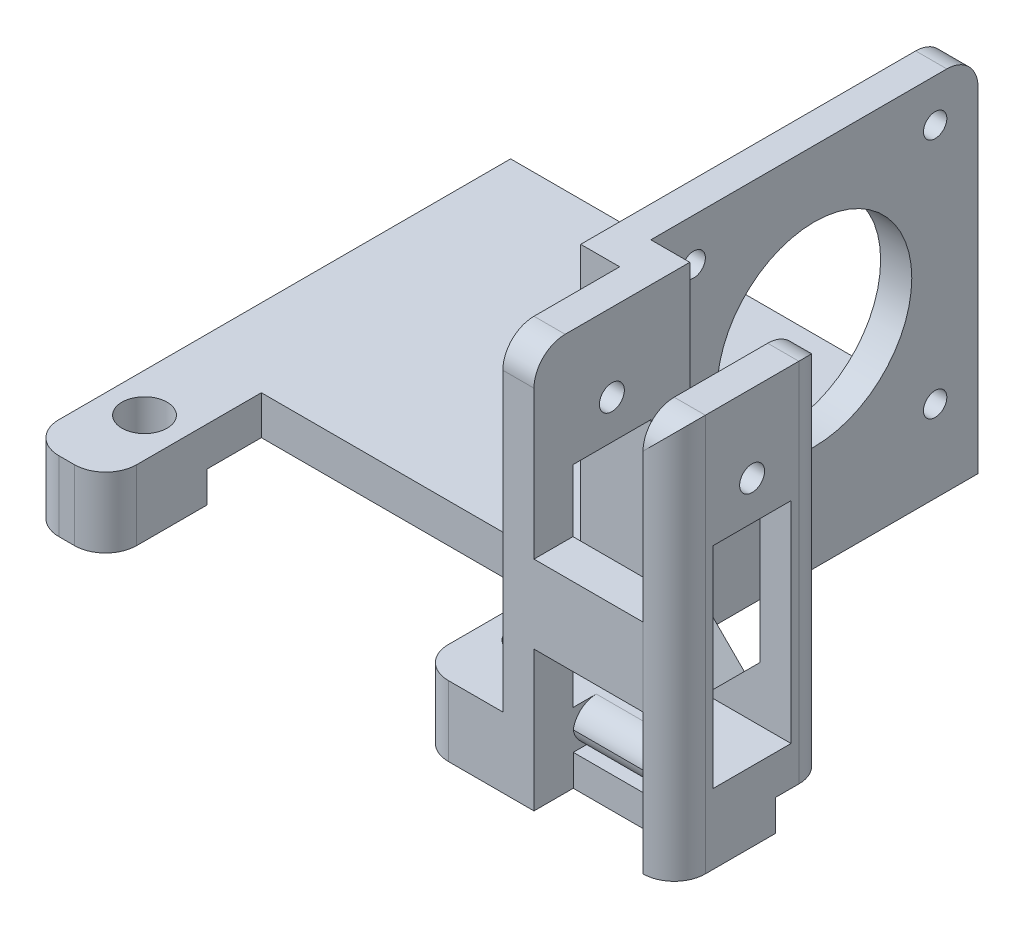
SolidWorks part; units mm, degrees
ref_plane "前视基准面" through (0, 0, 0) normal (0, 0, 1) x (1, 0, 0)
ref_plane "上视基准面" through (0, 0, 0) normal (0, 1, 0) x (1, 0, 0)
ref_plane "右视基准面" through (0, 0, 0) normal (1, 0, 0) x (0, 0, -1)
other "Configuration Table"
sketch "草图1" plane through (0, 0, 0) normal (0, 1, 0) x (1, 0, 0)
  line L1 (10, 0) -> (50, 0)
  line L2 (0, 0) -> (0, 42)
  line L3 (0, 42) -> (60, 42)
  line L4 (60, 0) -> (60, 42)
  line L6 (0, 0) -> (0, -20)
  line L7 (0, -20) -> (10, -20)
  line L8 (10, 0) -> (10, -20)
  line L14 (60, 0) -> (60, -20)
  line L15 (60, -20) -> (50, -20)
  line L16 (50, 0) -> (50, -20)
  point P11 (5, -20)
  dimension "D1" = 10
  dimension "D2" = 60
  dimension "D3" = 42
  dimension "D4" = 20
  dimension "D5" = 20
  dimension "D6" = 10
  dimension "D7" = 20
extrude "凸台-拉伸1" add sketch "草图1" along normal blind 5
sketch "草图3" plane through (0, 5, 0) normal (0, 1, 0) x (1, 0, 0)
  line L1 (56, 0) -> (60, 0)
  line L2 (56, 0) -> (56, 42)
  line L3 (56, 42) -> (60, 42)
  line L4 (60, 0) -> (60, 42)
  dimension "D1" = 4
extrude "凸台-拉伸2" add sketch "草图3" along normal blind 42
sketch "草图4" plane through (56, 0, 0) normal (-1, 0, 0) x (0, 0, 1)
  line L0 (-42, 47) -> (-36.5, 47) construction
  line L1 (-42, 47) -> (0, 47) construction
  line L2 (-36.5, 47) -> (-36.5, 41.5) construction
  line L3 (-36.5, 41.5) -> (-5.5, 41.5) construction
  line L4 (-5.5, 41.5) -> (-5.5, 10.5) construction
  line L5 (-5.5, 10.5) -> (-36.5, 10.5) construction
  circle A0 centre (-36.5, 41.5) radius 1.5
  circle A1 centre (-5.5, 41.5) radius 1.5
  circle A2 centre (-5.5, 10.5) radius 1.5
  circle A3 centre (-36.5, 10.5) radius 1.5
  dimension "D6" = 3
  dimension "D1" = 5.5
  dimension "D2" = 5.5
  dimension "D3" = 31
  dimension "D4" = 31
  dimension "D5" = 31
extrude "切除-拉伸1" cut sketch "草图4" against normal blind 42.5
sketch "草图5" plane through (56, 0, 0) normal (-1, 0, 0) x (0, 0, 1)
  line L0 (-42, 47) -> (0, 5) construction
  circle A0 centre (-21, 26) radius 12.5
  dimension "D1" = 25
extrude "切除-拉伸2" cut sketch "草图5" against normal blind 42.5
sketch "草图6" plane through (0, 5, 0) normal (0, 1, 0) x (1, 0, 0)
  line L0 (5, -20) -> (5, -10) construction
  line L1 (0, -20) -> (10, -20) construction
  line L2 (55, -20) -> (55, -10) construction
  line L3 (50, -20) -> (60, -20) construction
  circle A0 centre (55, -10) radius 1.5
  circle A1 centre (5, -10) radius 1.5
  dimension "D3" = 3
  dimension "D4" = 3
  dimension "D1" = 10
  dimension "D2" = 10
extrude "切除-拉伸3" cut sketch "草图6" against normal blind 42.5
sketch "草图7" plane through (60, 0, 0) normal (1, 0, 0) x (0, 0, -1)
  line L1 (-20, 5) -> (0, 5)
  line L2 (-20, 5) -> (-20, 0)
  line L3 (-20, 0) -> (0, 0)
  line L4 (0, 5) -> (0, 0)
extrude "凸台-拉伸3" add sketch "草图7" along normal blind 5
sketch "草图8" plane through (0, 5, 0) normal (0, 1, 0) x (1, 0, 0)
  line L0 (50, -20) -> (65, -20) construction
  line L1 (65, 0) -> (56, 0)
  line L2 (65, 0) -> (65, -20)
  line L3 (65, -20) -> (56, -20)
  line L4 (56, 0) -> (56, -5)
  line L5 (56, -15) -> (56, -20)
  line L6 (56, -5) -> (61, -5)
  line L8 (56, -15) -> (61, -15)
  line L9 (61, -5) -> (61, -15)
  dimension "D1" = 9
  dimension "D2" = 5
  dimension "D3" = 5
  dimension "D4" = 5
extrude "凸台-拉伸5" add sketch "草图8" along normal up to surface (42 mm away) up to face at (58, 47, -21)
sketch "草图11" plane through (65, 0, 0) normal (1, 0, 0) x (0, 0, -1)
  line L4 (-20, 0) -> (0, 0)
  line L5 (-20, 5) -> (-20, 0)
  line L6 (0, 5) -> (-20, 5)
  line L7 (0, 0) -> (0, 5)
  line L8 (-20, 0) -> (0, 0)
  line L9 (-20, 5) -> (-20, 0)
  line L10 (0, 5) -> (-20, 5)
  line L11 (0, 0) -> (0, 5)
  dimension "D1" = 0
extrude "凸台-拉伸6" add sketch "草图11" along normal blind 18
sketch "草图12" plane through (0, 5, 0) normal (0, 1, 0) x (1, 0, 0)
  line L0 (83, -20) -> (65, -20) construction
  line L1 (83, 0) -> (79, 0)
  line L2 (83, 0) -> (83, -20)
  line L3 (83, -20) -> (79, -20)
  line L4 (79, 0) -> (79, -20)
  dimension "D1" = 4
extrude "凸台-拉伸7" add sketch "草图12" along normal up to surface (42 mm away) up to face at (59.6, 47, -0.4)
sketch "草图13" plane through (83, 0, 0) normal (1, 0, 0) x (0, 0, -1)
  line L0 (0, 47) -> (-20, 47) construction
  circle A0 centre (-10, 37) radius 1.6
  dimension "D1" = 10
  dimension "D2" = 3.2
extrude "切除-拉伸4" cut sketch "草图13" against normal up to surface (22 mm away) up to face at (61, 26, 10)
sketch "草图15" plane through (61, 0, 0) normal (-1, 0, 0) x (0, 0, 1)
  line L0 (15, 47) -> (15, 5) construction
  line L1 (5, 5) -> (15, 5)
  line L2 (5, 5) -> (5, 32)
  line L3 (5, 32) -> (15, 32)
  line L4 (15, 5) -> (15, 32)
  circle A0 centre (10, 37) radius 1.6 construction
  dimension "D1" = 5
extrude "切除-拉伸5" cut sketch "草图15" against normal up to surface (22 mm away) up to face at (83, 37, 8.4)
sketch "草图16" plane through (0, 47, 0) normal (0, 1, 0) x (1, 0, 0)
  line L1 (61, -15) -> (56, -15)
  line L2 (61, -15) -> (61, -20)
  line L3 (61, -20) -> (56, -20)
  line L4 (56, -15) -> (56, -20)
extrude "切除-拉伸6" cut sketch "草图16" against normal up to surface (42 mm away) up to face at (55, 5, 11.5)
sketch "草图17" plane through (61, 0, 0) normal (-1, 0, 0) x (0, 0, 1)
  line L0 (5, 47) -> (5, 5) construction
  line L1 (15, 5) -> (5, 5)
  line L2 (15, 5) -> (15, 10)
  line L3 (15, 10) -> (5, 10)
  line L4 (5, 5) -> (5, 10)
  dimension "D1" = 5
extrude "凸台-拉伸8" add sketch "草图17" against normal up to surface (22 mm away) up to face at (83, 18.5, 10)
sketch "草图19" plane through (0, 10, 0) normal (0, 1, 0) x (1, 0, 0)
  line L8 (79, -15) -> (83, -15)
  line L9 (83, -15) -> (83, -5)
  line L10 (83, -5) -> (79, -5)
  line L11 (79, -5) -> (65, -5)
  line L12 (65, -5) -> (61, -5)
  line L13 (61, -5) -> (61, -15)
  line L14 (61, -15) -> (65, -15)
  line L15 (65, -15) -> (79, -15)
  line L16 (79, -15) -> (83, -15)
  line L17 (83, -15) -> (83, -5)
  line L18 (83, -5) -> (79, -5)
  line L19 (79, -5) -> (65, -5)
  line L20 (65, -5) -> (61, -5)
  line L21 (61, -5) -> (61, -15)
  line L22 (61, -15) -> (65, -15)
  line L23 (65, -15) -> (79, -15)
  dimension "D1" = 0
extrude "切除-拉伸7" cut sketch "草图19" against normal up to surface (5 mm away) up to face at (35.4, 5, 0.6)
fillet "圆角1" radius 4 9 edges at (83, 23.5, 0) (83, 23.5, 20) (0, 2.5, 20) (10, 2.5, 20) (50, 2.5, 20) (81, 47, 20) (63, 47, 20) (81, 47, 0) (58, 47, -42)
sketch "草图20" plane through (0, 0, 20) normal (0, 0, 1) x (1, 0, 0)
  line L1 (65, 5) -> (79, 5)
  line L2 (65, 5) -> (65, 0)
  line L3 (65, 0) -> (79, 0)
  line L4 (79, 5) -> (79, 0)
extrude "切除-拉伸8" cut sketch "草图20" against normal blind 5
fillet "圆角3" radius 3 2 edges at (72, 0, 15) (72, 5, 15)
sketch "草图21" plane through (0, 5, 0) normal (0, 1, 0) x (1, 0, 0)
  circle A0 centre (5, -10) radius 2.9
  circle A1 centre (55, -10) radius 2.9
  dimension "D1" = 5.8
  dimension "D2" = 5.8
extrude "切除-拉伸9" cut sketch "草图21" against normal offset from surface (3 mm away) 2 up to face at (55, 0, 11.5)
sketch "草图23" plane through (0, 0, 0) normal (0, -1, 0) x (1, 0, 0)
  line L0 (54, 20) -> (65, 20) construction
  line L1 (4, 20) -> (6, 20) construction
  line L2 (54, 20) -> (65, 20)
  line L3 (4, 20) -> (6, 20)
  line L4 (0, 16) -> (0, 7)
  line L5 (0, -42) -> (0, 16) construction
  line L6 (0, 7) -> (10, 7)
  line L7 (83, 16) -> (83, 4) construction
  line L8 (83, 7) -> (83, 16)
  line L9 (79, 20) -> (79, 14.958)
  line L10 (79, 14.958) -> (65, 14.958)
  line L11 (65, 12) -> (65, 20) construction
  line L12 (65, 14.958) -> (65, 20)
  line L13 (50, 16) -> (50, 7)
  line L14 (50, 0) -> (50, 16) construction
  line L16 (10, 16) -> (10, 0) construction
  line L17 (10, 7) -> (10, 16)
  line L18 (50, 7) -> (83, 7)
  arc A0 (83, 16) -> (79, 20) centre (79, 16) ccw construction
  arc A1 (54, 20) -> (50, 16) centre (54, 16) ccw construction
  arc A2 (10, 16) -> (6, 20) centre (6, 16) ccw construction
  arc A3 (4, 20) -> (0, 16) centre (4, 16) ccw construction
  arc A4 (83, 16) -> (79, 20) centre (79, 16) ccw
  arc A5 (54, 20) -> (50, 16) centre (54, 16) ccw
  arc A6 (10, 16) -> (6, 20) centre (6, 16) ccw
  arc A7 (4, 20) -> (0, 16) centre (4, 16) ccw
  dimension "D1" = 13
  dimension "D2" = 13
extrude "凸台-拉伸9" add sketch "草图23" along normal blind 4
sketch "草图24" plane through (0, 0, 0) normal (0, 1, 0) x (1, 0, 0)
  circle A0 centre (55, -10) radius 1.5 construction
  circle A1 centre (5, -10) radius 1.5 construction
  circle A2 centre (55, -10) radius 1.5
  circle A3 centre (5, -10) radius 1.5
extrude "切除-拉伸10" cut sketch "草图24" against normal blind 4
sketch "草图26" plane through (0, 2, 0) normal (0, 1, 0) x (1, 0, 0)
  circle A0 centre (55, -10) radius 2.9 construction
  circle A1 centre (5, -10) radius 2.9 construction
  circle A2 centre (55, -10) radius 2.9
  circle A3 centre (5, -10) radius 2.9
extrude "切除-拉伸15" cut sketch "草图26" against normal blind 4
chamfer "倒角1" distance 7 angle 45 2 edges at (65, 5, 2.5) (79, 5, 2.5)
sketch "草图28" plane through (79, 0, 0) normal (-1, 0, 0) x (0, 0, 1)
  line L0 (15, 5) -> (15, 32) construction
  line L1 (15, 24) -> (20, 24)
  line L2 (15, 24) -> (15, 14)
  line L3 (15, 14) -> (20, 14)
  line L4 (20, 24) -> (20, 14)
  line L5 (20, 5) -> (20, 43) construction
  line L6 (15, 32) -> (5, 32) construction
  dimension "D1" = 8
  dimension "D2" = 10
extrude "凸台-拉伸10" add sketch "草图28" along normal up to next
